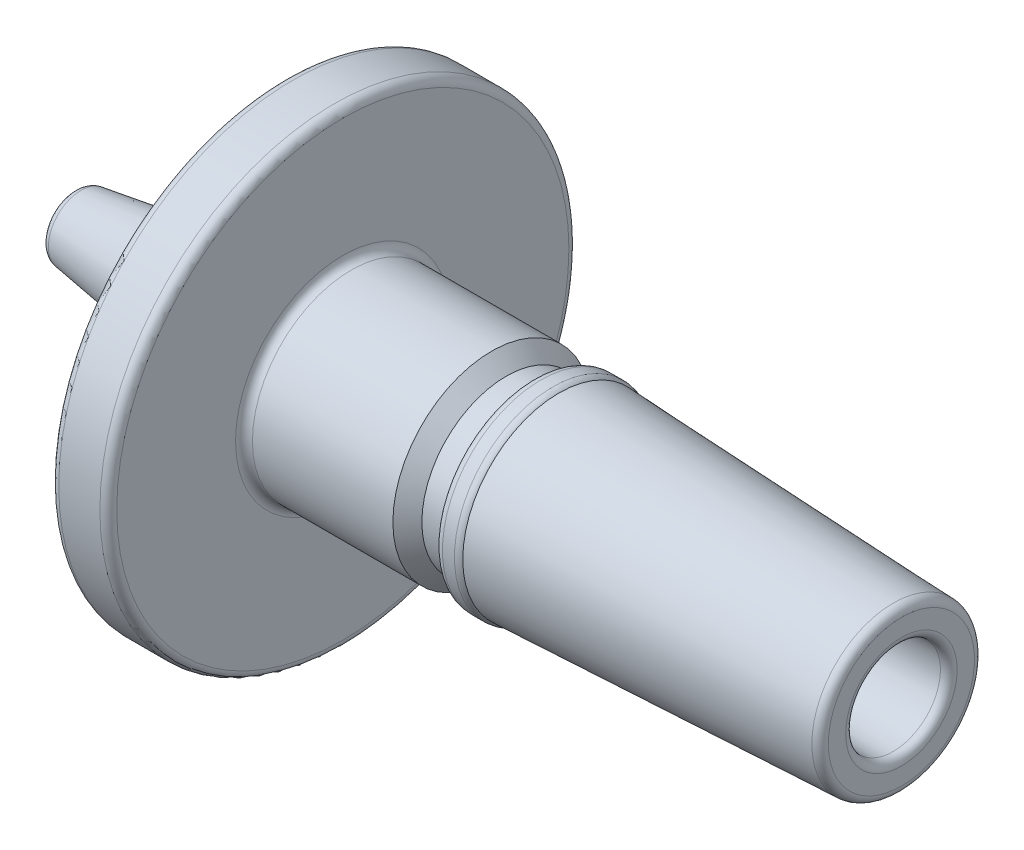
SolidWorks part; units mm, degrees
material "PC High Viscosity"
ref_plane "Front Plane" through (0, 0, 0) normal (0, 0, 1) x (1, 0, 0)
ref_plane "Top Plane" through (0, 0, 0) normal (0, 1, 0) x (1, 0, 0)
ref_plane "Right Plane" through (0, 0, 0) normal (1, 0, 0) x (0, 0, -1)
sketch "Sketch1" plane through (0, 0, 0) normal (0, 1, 0) x (1, 0, 0)
  line L0 (0, 0) -> (28.2389, 0) construction
  line L1 (1.397, 0.908) -> (14.859, 1.143)
  line L2 (14.859, 1.143) -> (14.859, 1.9558)
  line L3 (14.859, 1.9558) -> (6.604, 2.3162)
  line L4 (6.604, 2.3162) -> (6.604, 2.3749)
  line L5 (6.604, 2.3749) -> (5.969, 2.3749)
  line L6 (5.969, 2.3749) -> (5.969, 2.032)
  line L7 (5.969, 2.032) -> (5.334, 2.032)
  line L8 (5.334, 2.032) -> (4.9848, 2.3813)
  line L9 (4.9848, 2.3813) -> (1.397, 2.3812)
  line L10 (1.397, 2.3812) -> (1.397, 5.6515)
  line L11 (1.397, 5.6515) -> (0, 5.6515)
  line L12 (0, 5.6515) -> (0, 1.143)
  line L13 (0, 1.143) -> (-1.27, 0.9525)
  line L14 (-1.27, 0.9525) -> (-2.54, 0.9525)
  line L15 (-2.54, 0.9525) -> (-2.54, 1.143)
  line L16 (-2.54, 1.143) -> (-5.08, 0.762)
  line L17 (-5.08, 0.762) -> (-5.08, 0.635)
  line L18 (-5.08, 0.635) -> (1.397, 0.635)
  line L19 (1.397, 0.635) -> (1.397, 0.908)
  dimension "D1" = 14.859
  dimension "D2" = 1.397
  dimension "D3" = 11.303
  dimension "D4" = 2.286
  dimension "D5" = 0.8128
  dimension "D6" = 1
  dimension "D7" = 2.5
  dimension "D8" = 8.255
  dimension "D9" = 4.7498
  dimension "D10" = 0.635
  dimension "D11" = 4.064
  dimension "D12" = 0.635
  dimension "D13" = 4.7625
  dimension "D14" = 135
  dimension "D15" = 2.286
  dimension "D16" = 1.905
  dimension "D17" = 1.27
  dimension "D18" = 2.54
  dimension "D19" = 1.27
  dimension "D20" = 5.08
  dimension "D21" = 2.286
  dimension "D22" = 1.524
revolve "Revolve1" add sketch "Sketch1" angle 360 about L0
fillet "Fillet1" radius 0.2032 10 edges at (14.859, 0, 1.143) (6.604, 0, 2.3749) (5.969, 0, 2.3749) (14.859, 0, 1.9558) (-5.08, 0, 0.762) (-1.27, 0, 0.9525) (0, 0, 1.143) (0, 0, 5.6515) (1.397, 0, 2.3812) (1.397, 0, 5.6515)
